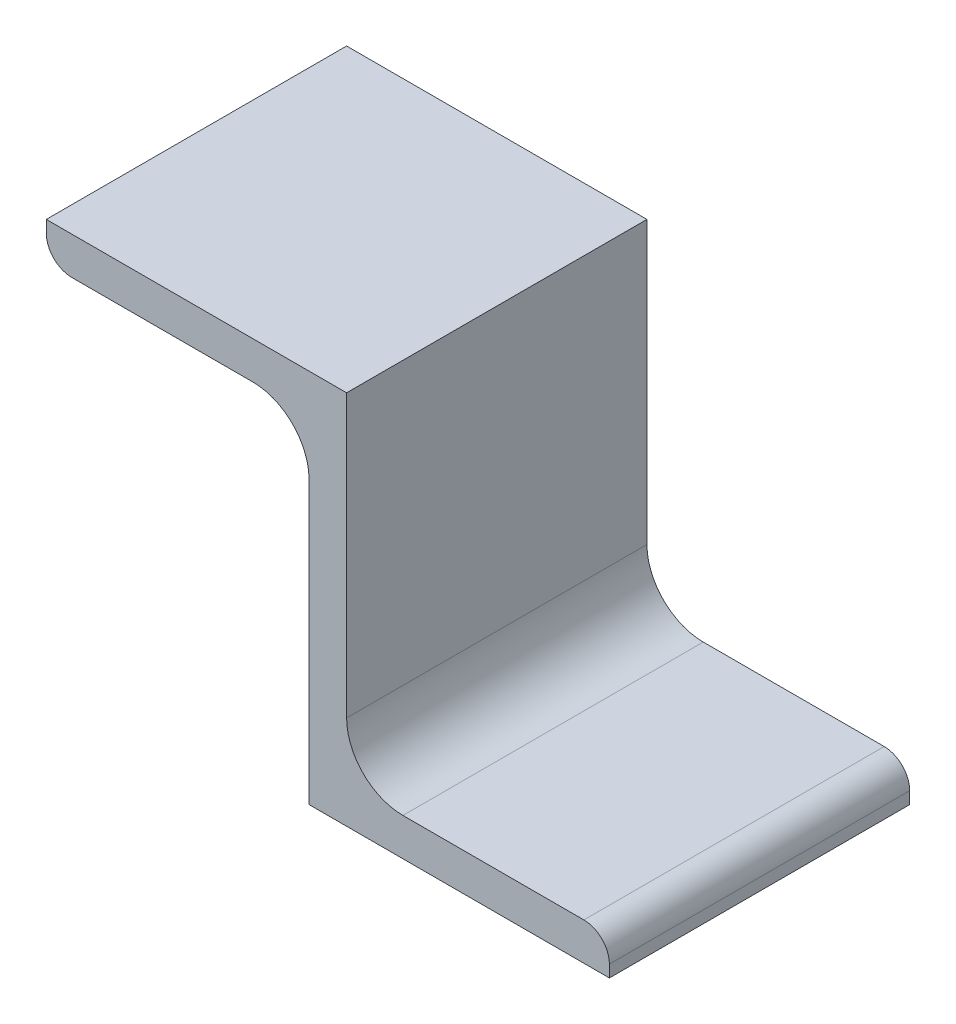
SolidWorks part; units mm, degrees
ref_plane "Plane1" through (0, 0, 0) normal (0, 0, 1) x (1, 0, 0)
ref_plane "Plane2" through (0, 0, 0) normal (0, 1, 0) x (-1, 0, 0)
ref_plane "Plane3" through (0, 0, 0) normal (1, 0, 0) x (0, 0, -1)
sketch "Sketch1" plane through (0, 0, 0) normal (0, 0, 1) x (1, 0, 0)
  line L0 (0, 0) -> (0, 23.8125)
  line L1 (15.6984, 0) -> (-15.6984, 0) construction
  line L2 (0, 0) -> (25.4, 0)
  line L3 (23.241, 3.175) -> (7.9375, 3.175)
  line L4 (3.175, 31.75) -> (3.175, 7.9375)
  line L5 (0, -15.6984) -> (0, 15.6984) construction
  line L6 (-22.225, 31.75) -> (3.175, 31.75)
  line L7 (25.4, 0) -> (25.4, 1.016)
  line L8 (-20.066, 28.575) -> (-4.7625, 28.575)
  line L9 (-22.225, 30.734) -> (-22.225, 31.75)
  arc A0 (0, 23.8125) -> (-4.7625, 28.575) centre (-4.7625, 23.8125) ccw
  arc A1 (3.175, 7.9375) -> (7.9375, 3.175) centre (7.9375, 7.9375) ccw
  arc A2 (25.4, 1.016) -> (23.241, 3.175) centre (23.241, 1.016) ccw
  arc A3 (-22.225, 30.734) -> (-20.066, 28.575) centre (-20.066, 30.734) ccw
  dimension "d" = 31.75
extrude "Base-Zee" add sketch "Sketch1" along normal mid plane 25.4
